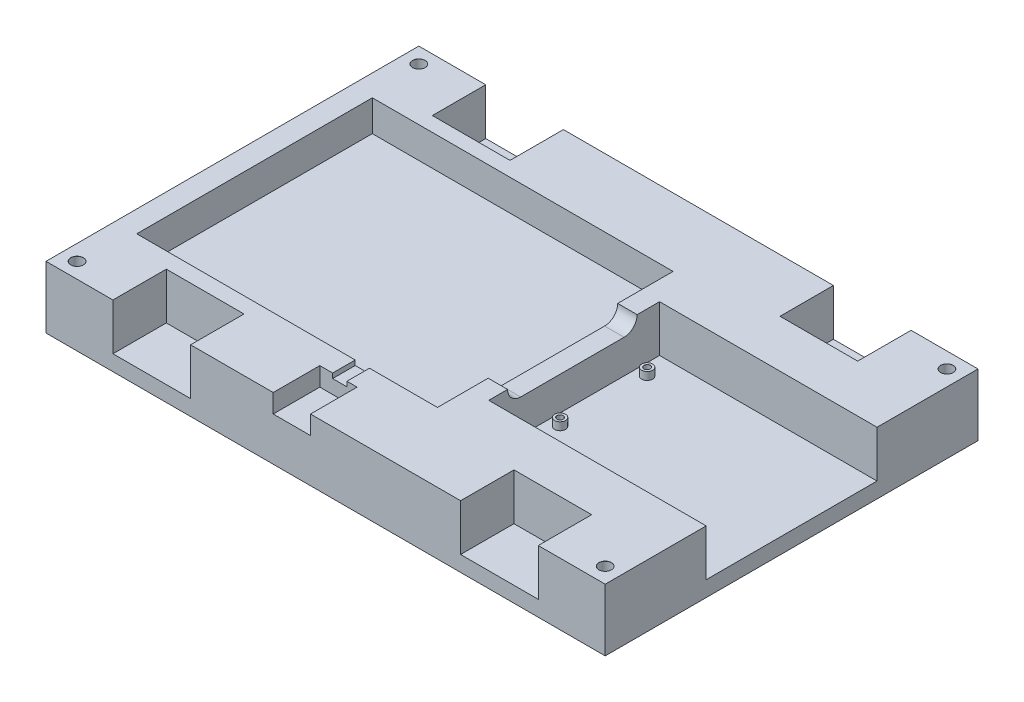
SolidWorks part; units mm, degrees
ref_plane "Front Plane" through (0, 0, 0) normal (0, 0, 1) x (1, 0, 0)
ref_plane "Top Plane" through (0, 0, 0) normal (0, 1, 0) x (1, 0, 0)
ref_plane "Right Plane" through (0, 0, 0) normal (1, 0, 0) x (0, 0, -1)
sketch "Sketch1" plane through (0, 0, 0) normal (0, 1, 0) x (1, 0, 0)
  line L1 (90, 60) -> (-90, 60)
  line L2 (90, 60) -> (90, -60)
  line L3 (90, -60) -> (-90, -60)
  line L4 (-90, 60) -> (-90, -60)
  line L5 (90, 60) -> (-90, -60) construction
  line L6 (90, -60) -> (-90, 60) construction
  point P0 (0, 0)
  dimension "D1" = 180
  dimension "D2" = 120
extrude "Boss-Extrude1" add sketch "Sketch1" along normal blind 20
sketch "Sketch2" plane through (0, 20, 0) normal (0, 1, 0) x (1, 0, 0)
  line L0 (90, 0) -> (90, 27.5)
  line L1 (90, -60) -> (90, 60) construction
  line L2 (90, 0) -> (90, -27.5)
  line L3 (90, 27.5) -> (20, 27.5)
  line L4 (20, 27.5) -> (20, -27.5)
  line L5 (20, -27.5) -> (90, -27.5)
  dimension "D1" = 27.5
  dimension "D2" = 27.5
  dimension "D3" = 70
extrude "Cut-Extrude1" cut sketch "Sketch2" against normal blind 15
sketch "Sketch3" plane through (0, 20, 0) normal (0, 1, 0) x (1, 0, 0)
  line L0 (-90, -60) -> (90, -60) construction
  line L1 (68.4559, -77.185) -> (43.4559, -77.185)
  line L2 (68.4559, -77.185) -> (68.4559, -42.815)
  line L3 (68.4559, -42.815) -> (43.4559, -42.815)
  line L4 (43.4559, -77.185) -> (43.4559, -42.815)
  line L5 (68.4559, -77.185) -> (43.4559, -42.815) construction
  line L6 (68.4559, -42.815) -> (43.4559, -77.185) construction
  point P0 (55.9559, -60)
  dimension "D1" = 25
  dimension "D2" = 34.37
extrude "Cut-Extrude2" cut sketch "Sketch3" against normal blind 15
mirror "Mirror1" about plane through (0, 0, 0) normal (1, 0, 0) of "Cut-Extrude2"
mirror "Mirror2" about plane through (0, 0, 0) normal (0, 0, 1) of "Mirror1", "Cut-Extrude2"
sketch "Sketch4" plane through (0, 20, 0) normal (0, 1, 0) x (1, 0, 0)
  line L1 (-83.0687, 38.109) -> (13.7398, 38.109)
  line L2 (-83.0687, 38.109) -> (-83.0687, -37.7325)
  line L3 (-83.0687, -37.7325) -> (13.7398, -37.7325)
  line L4 (13.7398, 38.109) -> (13.7398, -37.7325)
  dimension "D1" = 75.8415
  dimension "D2" = 96.8085
extrude "Cut-Extrude4" cut sketch "Sketch4" against normal blind 10
sketch "Sketch6" plane through (0, 5, 0) normal (0, 1, 0) x (1, 0, 0)
  line L0 (-62.6949, -357.8384) -> (-777.3616, -357.8384) construction
  circle A0 centre (23.7402, 19.7599) radius 1.7503
  circle A1 centre (23.7402, -8.258) radius 1.75
  circle A3 centre (74.9588, -23.6924) radius 1.75
  dimension "D1" = 3.5
  dimension "D2" = 3.5007
  dimension "D4" = 3.5
extrude "Boss-Extrude2" add sketch "Sketch6" along normal blind 2.5
hole_wizard "Ø2.0 (2) Diameter Hole1" positions "3DSketch7" profile "Sketch12" hole size "Ø2.0" standard "AS"
sketch3d "3DSketch7"
  line L0 (23.7402, 7.5, -19.7599) -> (23.7402, 5, -19.7599) construction
  line L1 (23.7402, 7.5, 8.258) -> (23.7402, 5, 8.258) construction
  line L2 (74.9588, 7.5, 23.6924) -> (74.9588, 5, 23.6924) construction
  point P0 (23.7402, 7.5, -19.7599)
  point P4 (23.7402, 7.5, 8.258)
  point P8 (74.9588, 7.5, 23.6924)
sketch "Sketch12" plane through (23.7402, 7.5, -19.7599) normal (1, 0, 0) x (0, 0, 1)
  line L0 (0, 0) -> (0, 2.6009)
  line L1 (0, 2.6009) -> (1, 2)
  line L2 (1, 2) -> (1, 0.0241)
  line L3 (1, 0.0241) -> (1.025, 0)
  line L5 (1.025, 0) -> (0, 0)
  line L6 (-1, 0.0241) -> (-1.025, 0) construction
  line L10 (0, 2.6009) -> (-1, 2) construction
  line L11 (0, -6.35) -> (0, 107.95) construction
  dimension "Hole Dia." = 2
  dimension "Hole Depth" = 2
  dimension "Near C'Sink Dia." = 2.05
  dimension "Near C'Sink Angle" = 92
  dimension "Drill Angle" = 118
sketch "Sketch14" plane through (0, 20, 0) normal (0, 1, 0) x (1, 0, 0)
  line L0 (-90, 60) -> (-90, 55)
  line L1 (-90, 60) -> (-90, -60) construction
  line L2 (-90, 55) -> (-85, 55)
  line L3 (90, 60) -> (90, 55)
  line L4 (90, 27.5) -> (90, 60) construction
  line L5 (90, 55) -> (85, 55)
  line L6 (-90, -60) -> (-90, -55)
  line L7 (-90, -55) -> (-85, -55)
  line L8 (90, -60) -> (90, -55)
  line L9 (90, -60) -> (90, -27.5) construction
  line L10 (90, -55) -> (85, -55)
  dimension "D1" = 5
  dimension "D2" = 5
  dimension "D3" = 5
  dimension "D4" = 5
  dimension "D5" = 5
  dimension "D6" = 5
  dimension "D7" = 5
  dimension "D8" = 5
hole_wizard "Ø4.0 (4) Diameter Hole3" positions "3DSketch11" profile "Sketch18" hole size "Ø4.0" standard "AS"
sketch3d "3DSketch11"
  point P0 (-85, 20, -55)
  point P3 (85, 20, -55)
  point P6 (85, 20, 55)
  point P9 (-85, 20, 55)
sketch "Sketch18" plane through (-85, 20, -55) normal (1, 0, 0) x (0, 0, 1)
  line L0 (0, 0) -> (0, 6.2017)
  line L1 (0, 6.2017) -> (2, 5)
  line L2 (2, 5) -> (2, 0.0241)
  line L3 (2, 0.0241) -> (2.025, 0)
  line L5 (2.025, 0) -> (0, 0)
  line L6 (-2, 0.0241) -> (-2.025, 0) construction
  line L10 (0, 6.2017) -> (-2, 5) construction
  line L11 (0, -6.35) -> (0, 107.95) construction
  dimension "Hole Dia." = 4
  dimension "Hole Depth" = 5
  dimension "Near C'Sink Dia." = 4.05
  dimension "Near C'Sink Angle" = 92
  dimension "Drill Angle" = 118
sketch "Sketch19" plane through (20, 0, 0) normal (1, 0, 0) x (0, 0, -1)
  line L0 (-17.2052, 20) -> (16.0767, 20) construction
  line L1 (27.5, 20) -> (-27.5, 20) construction
  line L2 (-17.2052, 24.2066) -> (16.0767, 24.2066)
  line L3 (-17.2052, 15.7934) -> (16.0767, 15.7934)
  arc A0 (-17.2052, 24.2066) -> (-17.2052, 15.7934) centre (-17.2052, 20) ccw
  arc A1 (16.0767, 15.7934) -> (16.0767, 24.2066) centre (16.0767, 20) ccw
  point P4 (-0.5642, 20)
extrude "Cut-Extrude5" cut sketch "Sketch19" against normal blind 10
sketch "Sketch21" plane through (0, 0, 60) normal (0, 0, 1) x (1, 0, 0)
  line L0 (-43.4559, 20) -> (43.4559, 20) construction
  line L1 (-4.863, 20) -> (-16.863, 20)
  line L2 (-4.863, 20) -> (-4.863, 14)
  line L3 (-4.863, 14) -> (-16.863, 14)
  line L4 (-16.863, 20) -> (-16.863, 14)
  dimension "D1" = 6
  dimension "D2" = 12
extrude "Cut-Extrude6" cut sketch "Sketch21" against normal blind 15
sketch "Sketch22" plane through (0, 0, 37.7325) normal (0, 0, -1) x (-1, 0, 0)
  line L0 (83.0687, 20) -> (-13.7398, 20) construction
  line L1 (12.735, 20) -> (8.1365, 20)
  line L2 (12.735, 20) -> (12.735, 18.4462)
  line L3 (12.735, 18.4462) -> (8.1365, 18.4462)
  line L4 (8.1365, 20) -> (8.1365, 18.4462)
extrude "Cut-Extrude7" cut sketch "Sketch22" against normal blind 15
